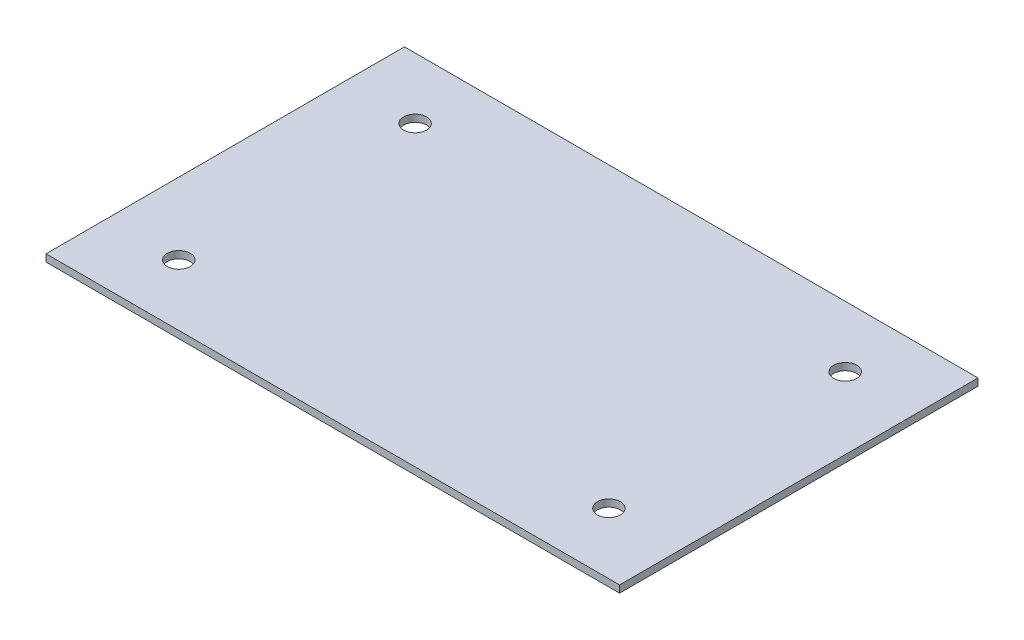
SolidWorks part; units mm, degrees
ref_plane "Спереди" through (0, 0, 0) normal (0, 0, 1) x (1, 0, 0)
ref_plane "Сверху" through (0, 0, 0) normal (0, 1, 0) x (1, 0, 0)
ref_plane "Справа" through (0, 0, 0) normal (1, 0, 0) x (0, 0, -1)
sketch "Эскиз1" plane through (0, 0, 0) normal (0, 1, 0) x (1, 0, 0)
  line L0 (140, 17.0342) -> (20, 17.0342) construction
  line L5 (0, 0) -> (160, 0)
  line L6 (0, 0) -> (0, 100)
  line L7 (0, 100) -> (160, 100)
  line L8 (160, 0) -> (160, 100)
  line L9 (160, 50) -> (0, 50) construction
  circle A0 centre (140, 17.0342) radius 3.2
  circle A1 centre (20, 17.0342) radius 3.2
  circle A2 centre (140, 82.9658) radius 3.2
  circle A3 centre (20, 82.9658) radius 3.2
  dimension "D1" = 160
  dimension "D2" = 100
extrude "Бобышка-Вытянуть1" add sketch "Эскиз1" along normal blind 2
